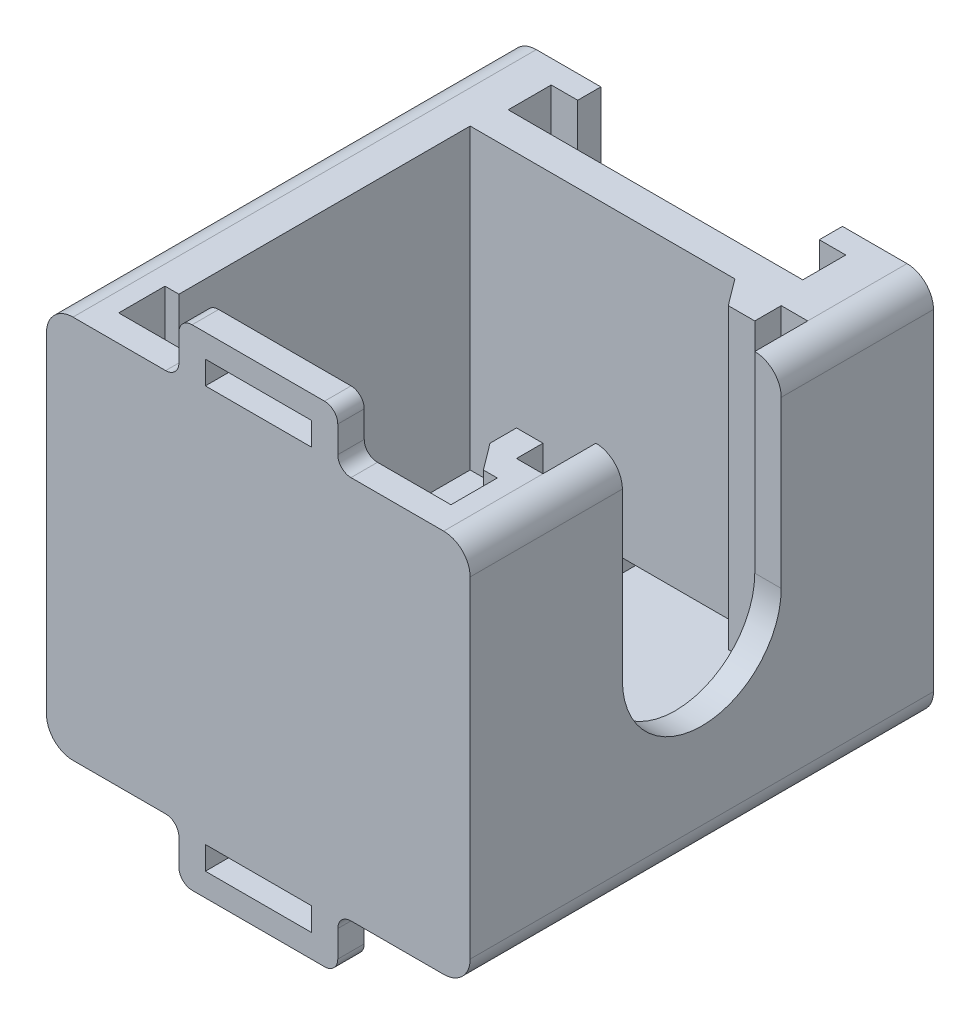
SolidWorks part; units mm, degrees
material "UNOBTANIUM"
ref_plane "Top Plane" through (0, 0, 0) normal (0, 0, 1) x (1, 0, 0)
ref_plane "Right Plane" through (0, 0, 0) normal (0, 1, 0) x (1, 0, 0)
ref_plane "Front Plane" through (0, 0, 0) normal (1, 0, 0) x (0, 0, -1)
ref_axis "x-axis" through (-17.6, 0, 0) along (1, 0, 0)
ref_axis "y-axis" through (0, -14.85, 0) along (0, 1, 0)
ref_axis "z-axis" through (0, 0, 36.75) along (0, 0, -1)
sketch "Sketch1" plane through (0, 0, 0) normal (0, 0, 1) x (1, 0, 0)
  line L1 (-16, 14.5) -> (16, 14.5)
  line L2 (-16, 14.5) -> (-16, -14.5)
  line L3 (-16, -14.5) -> (16, -14.5)
  line L4 (16, 14.5) -> (16, -14.5)
  line L5 (-16, 14.5) -> (16, -14.5) construction
  line L6 (-16, -14.5) -> (16, 14.5) construction
  point P0 (0, 0)
  dimension "D1" = 32
  dimension "D2" = 29
extrude "Boss-Extrude1" add sketch "Sketch1" along normal blind 35
fillet "Fillet1" radius 2 4 edges at (16, -14.5, 17.5) (16, 14.5, 17.5) (-16, -14.5, 17.5) (-16, 14.5, 17.5)
sketch "Sketch2" plane through (0, -14.5, 0) normal (0, -1, 0) x (1, 0, 0)
  line L0 (-9.125, 0) -> (-9.125, 1.75)
  line L1 (-14, 0) -> (14, 0) construction
  line L2 (-9.125, 1.75) -> (-11.125, 1.75)
  line L3 (-11.125, 1.75) -> (-11.125, 5)
  line L4 (-11.125, 5) -> (11.125, 5)
  line L5 (11.125, 5) -> (11.125, 1.75)
  line L6 (11.125, 1.75) -> (9.125, 1.75)
  line L7 (9.125, 1.75) -> (9.125, 0)
  line L9 (-9.125, 0) -> (9.125, 0)
  point P4 (0, 0)
  dimension "D1" = 18.25
  dimension "D2" = 1.75
  dimension "D3" = 3.25
  dimension "D4" = 22.25
extrude "Slot for Coil" cut sketch "Sketch2" against normal through all both and the other way through all
sketch "Sketch3" plane through (0, -14.5, 0) normal (0, -1, 0) x (1, 0, 0)
  line L0 (-9.125, 0) -> (-9.125, 1.75)
  line L1 (-9.125, 1.75) -> (-11.125, 1.75)
  line L2 (-11.125, 1.75) -> (-11.125, 5)
  line L3 (-11.125, 5) -> (11.125, 5)
  line L4 (11.125, 5) -> (11.125, 1.75)
  line L5 (11.125, 1.75) -> (9.125, 1.75)
  line L6 (9.125, 1.75) -> (9.125, 0)
  line L7 (9.125, 0) -> (-9.125, 0)
extrude "Boss-Extrude2" add sketch "Sketch3" against normal blind 6.5
sketch "Sketch4" plane through (0, 0, 1.75) normal (0, 0, -1) x (-1, 0, 0)
  line L1 (-9.125, 7.5) -> (-9.125, 6.5)
  line L2 (-9.125, 14.5) -> (-9.125, -8) construction
  arc A0 (-9.125, 7.5) -> (-9.125, 6.5) centre (-9.5, 7) cw
  dimension "D1" = 0.625
  dimension "D2" = 0.25
  dimension "D3" = 7
extrude "Boss-Extrude3" add sketch "Sketch4" along normal up to surface (1.75 mm away) up to face at (0, 1.0833, 0)
mirror "Mirror1" about plane through (0, 0, 0) normal (1, 0, 0) of "Boss-Extrude3"
sketch "Sketch5" plane through (0, 0, 0) normal (0, 0, -1) x (-1, 0, 0)
  line L0 (9.125, -8) -> (-9.125, -8) construction
  line L1 (-1, -8) -> (1, -8)
  line L2 (-1, -8) -> (-1, -14.5)
  line L3 (-1, -14.5) -> (1, -14.5)
  line L4 (1, -8) -> (1, -14.5)
  line L5 (14, -14.5) -> (-14, -14.5) construction
  point P8 (0, -8)
  dimension "D1" = 2
extrude "slot to feed in wire" cut sketch "Sketch5" against normal offset from surface (33 mm away) 2 up to face at (0, 0, 35)
sketch "Sketch6" plane through (0, 14.5, 0) normal (0, 1, 0) x (1, 0, 0)
  line L7 (11.5, -7.5) -> (-11.5, -7.5)
  line L8 (11.125, -5) -> (-11.125, -5) construction
  line L9 (0, -7.5) -> (0, -5) construction
  line L12 (-12.55, -33) -> (-12.55, -29.5)
  line L13 (-12.55, -29.5) -> (-11.5, -29.5)
  line L14 (-11.5, -29.5) -> (-11.5, -7.5)
  line L16 (12.55, -33) -> (12.55, -29.5)
  line L17 (12.55, -29.5) -> (11.5, -29.5)
  line L18 (11.5, -29.5) -> (11.5, -7.5)
  line L19 (-12.55, -33) -> (12.55, -33)
  line L20 (14, -35) -> (-14, -35) construction
  dimension "D1" = 2.5
  dimension "D2" = 3.5
  dimension "D3" = 1.05
  dimension "D4" = 23
  dimension "D5" = 2
  dimension "D6" = 3.5
  dimension "D7" = 1.05
extrude "slot fo PCB" cut sketch "Sketch6" against normal up to surface (22.5 mm away) up to face at (7.0833, -8, 2.25)
sketch "Sketch7" plane through (0, -14.5, 0) normal (0, -1, 0) x (1, 0, 0)
  line L0 (1, 0) -> (14, 0) construction
  line L1 (1, 0) -> (-1, 0)
  line L2 (1, 0) -> (1, 33)
  line L3 (1, 33) -> (-1, 33)
  line L4 (-1, 0) -> (-1, 33)
  line L5 (1, 33) -> (1, 0) construction
extrude "Boss-Extrude4" add sketch "Sketch7" against normal offset from surface (2.5 mm away) 4 up to face at (7.0833, -8, 2.25)
fillet "Fillet2" radius 6 1 edges at (0, -12, 33)
ref_axis "Axis1" through (63.07, 0, 17.75) along (-1, 0, 0)
ref_plane "Plane1" through (0, 0, 17.75) normal (0, 0, -1) x (-1, 0, 0)
sketch "Sketch11" plane through (16, 0, 44) normal (1, 0, 0) x (0, 0, -1)
  line L0 (26.5, 25) -> (26.5, 0) construction
  line L4 (32.5, 25) -> (32.5, 0)
  line L5 (20.5, 25) -> (20.5, 0)
  line L6 (9, 12.5) -> (44, 12.5) construction
  line L7 (26.5, 0) -> (44, 0) construction
  line L8 (9, 12.5) -> (9, -12.5) construction
  arc A2 (32.5, 25) -> (20.5, 25) centre (26.5, 25) ccw
  arc A3 (20.5, 0) -> (32.5, 0) centre (26.5, 0) ccw
  point P2 (26.5, 12.5)
  dimension "D1" = 12
  dimension "D2" = 17.5
extrude "Rod Mount Slot" cut sketch "Sketch11" against normal up to next
sketch "Sketch14" plane through (0, 14.5, 0) normal (0, 1, 0) x (1, 0, 0)
  line L7 (14, -35) -> (14, -23.5) construction
  line L8 (11.5, -7.5) -> (14, -7.5)
  line L9 (11.5, -7.5) -> (11.5, -27.5)
  line L10 (11.5, -27.5) -> (14, -27.5)
  line L11 (14, -7.5) -> (14, -27.5)
  line L13 (12.55, -29.5) -> (11.5, -29.5) construction
  dimension "D2" = 2
extrude "Side cavity for mount plate" cut sketch "Sketch14" against normal up to surface (22.5 mm away) up to face at (-8.35, -8, 23.219)
sketch "Sketch16" plane through (0, 14.5, 0) normal (0, 1, 0) x (1, 0, 0)
  line L0 (1, -7.5) -> (14, -7.5) construction
  line L12 (12, -7.5) -> (10, -7.5)
  line L15 (12, -7.5) -> (12, -9.5)
  line L16 (12, -9.5) -> (10, -9.5)
  line L17 (10, -7.5) -> (10, -9.5)
  line L18 (14, -11.5) -> (14, -7.5) construction
  line L19 (14, -27.5) -> (11.5, -27.5) construction
  line L20 (12, -27.5) -> (10, -27.5)
  line L21 (12, -27.5) -> (12, -25.5)
  line L22 (12, -25.5) -> (10, -25.5)
  line L23 (10, -27.5) -> (10, -25.5)
  line L24 (14, -27.5) -> (14, -23.5) construction
  line L25 (14, -7.5) -> (14, -27.5) construction
  dimension "D6" = 2
  dimension "D7" = 2
  dimension "D8" = 2
  dimension "D9" = 2
  dimension "D10" = 4
extrude "Side stops for mount plate" add sketch "Sketch16" against normal up to surface (22.5 mm away) up to face at (-8.35, -8, 23.219)
sketch "Sketch20" plane through (0, 14.5, 0) normal (0, 1, 0) x (1, 0, 0)
  line L7 (11.5, -29.5) -> (10, -27.5)
  line L8 (10, -27.5) -> (11.5, -27.5)
  line L9 (11.5, -27.5) -> (11.5, -29.5)
  line L10 (10, -9.5) -> (8.5, -7.5)
  line L11 (10, -7.5) -> (-11.5, -7.5) construction
  line L12 (8.5, -7.5) -> (10, -7.5)
  line L13 (10, -7.5) -> (10, -9.5)
extrude "Boss-Extrude6" add sketch "Sketch20" against normal up to surface (22.5 mm away) up to face at (-8.35, -8, 23.219)
sketch "Sketch21" plane through (0, 14.5, 0) normal (0, 1, 0) x (-1, 0, 0)
  line L0 (0, 0) -> (0, 35) construction
  line L1 (-14, 35) -> (14, 35) construction
  line L2 (12.55, 33) -> (-12.55, 33) construction
  line L3 (-6, 35) -> (6, 35)
  line L4 (-6, 35) -> (-6, 33)
  line L5 (-6, 33) -> (6, 33)
  line L6 (6, 35) -> (6, 33)
  point P12 (0, 35)
  dimension "D1" = 12
extrude "Boss-Extrude7" add sketch "Sketch21" along normal blind 4
sketch "Sketch23" plane through (0, 0, 35) normal (0, 0, 1) x (1, 0, 0)
  line L0 (0, 0) -> (0, 18.5) construction
  line L1 (-6, 14.5) -> (-14, 14.5) construction
  line L3 (-4, 16.75) -> (4, 16.75)
  line L4 (-4, 16.75) -> (-4, 15)
  line L5 (-4, 15) -> (4, 15)
  line L6 (4, 16.75) -> (4, 15)
  line L7 (-6, 18.5) -> (6, 18.5) construction
  point P3 (0, 16.75)
  dimension "D1" = 1.75
  dimension "D2" = 8
  dimension "D3" = 0.5
extrude "Cut-Extrude7" cut sketch "Sketch23" against normal up to next
mirror "Mirror3" about plane through (0, 0, 0) normal (0, 1, 0) of "Boss-Extrude7", "Cut-Extrude7"
fillet "Fillet3" radius 1 8 edges at (-6, 14.5, 34) (6, 14.5, 34) (6, 18.5, 34) (-6, 18.5, 34) (6, -14.5, 34) (-6, -14.5, 34) (6, -18.5, 34) (-6, -18.5, 34)
sketch "Sketch26" plane through (-16, 0, 0) normal (1, 0, 0) x (0, 0, -1)
  circle A0 centre (-23.015, -2.89) radius 5.25
  dimension "D1" = 10.5
extrude "Cut-Extrude8" cut sketch "Sketch26" along normal up to next
